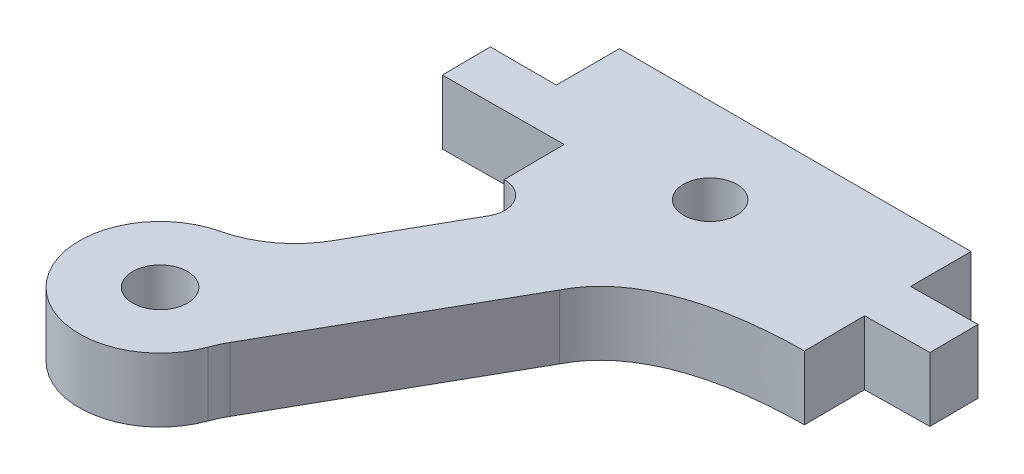
SolidWorks part; units mm, degrees
ref_plane "Front Plane" through (0, 0, 0) normal (0, 0, 1) x (1, 0, 0)
ref_plane "Top Plane" through (0, 0, 0) normal (0, 1, 0) x (1, 0, 0)
ref_plane "Right Plane" through (0, 0, 0) normal (1, 0, 0) x (0, 0, -1)
sketch "Sketch1" plane through (0, 0, 0) normal (0, 1, 0) x (1, 0, 0)
  line L0 (107.9066, 111.4178) -> (109.7939, 109.5579) construction
  line L1 (107.9202, 109.5441) -> (109.7803, 111.4315) construction
  line L2 (112.7322, 126.6373) -> (112.7541, 123.6373)
  line L3 (112.7322, 126.6373) -> (106.7324, 126.5933)
  line L4 (118.8599, 120.2646) -> (112.9502, 109.8535)
  line L5 (113.9088, 121.6708) -> (111.1322, 116.7792)
  line L6 (106.7148, 128.9932) -> (106.7324, 126.5933)
  line L7 (106.7148, 128.9932) -> (109.9895, 128.9932)
  line L8 (109.9895, 128.9932) -> (109.9895, 132.125)
  line L9 (109.9895, 132.125) -> (127.4143, 132.125)
  line L10 (127.4143, 129.1251) -> (127.4143, 132.125)
  line L11 (130.7141, 129.169) -> (127.4143, 129.1251)
  line L12 (130.7141, 129.169) -> (130.7317, 126.7691)
  line L13 (130.7317, 126.7691) -> (127.5322, 126.7252)
  line L14 (127.5322, 126.7252) -> (127.5538, 123.7252)
  line L15 (117.7795, 128.8112) -> (119.667, 126.9511) construction
  line L16 (119.6532, 128.825) -> (117.7931, 126.9375) construction
  circle A0 centre (108.8502, 110.4879) radius 1.36
  arc A1 (107.9318, 114.381) -> (112.605, 109.1089) centre (108.8502, 110.4879) ccw
  arc A2 (112.605, 109.1089) -> (112.9502, 109.8535) centre (117.2985, 107.3853) cw
  arc A3 (107.9318, 114.381) -> (111.1322, 116.7792) centre (106.7839, 119.2475) ccw
  arc A4 (112.7541, 123.6373) -> (113.9088, 121.6708) centre (112.7877, 122.3348) cw
  circle A5 centre (118.7232, 127.8812) radius 1.325
  spline S105 degree 3 poles (118.8599, 120.2646) (120.418, 123.3584) (125.112, 123.7074) (127.5538, 123.7252) knots 0.666667 0.666667 0.666667 0.666667 0.708333 0.708333 0.708333 0.708333
  dimension "D1" = 2.72
  dimension "D2" = 8
  dimension "D3" = 5
extrude "Boss-Extrude1" add sketch "Sketch1" along normal blind 3.175
